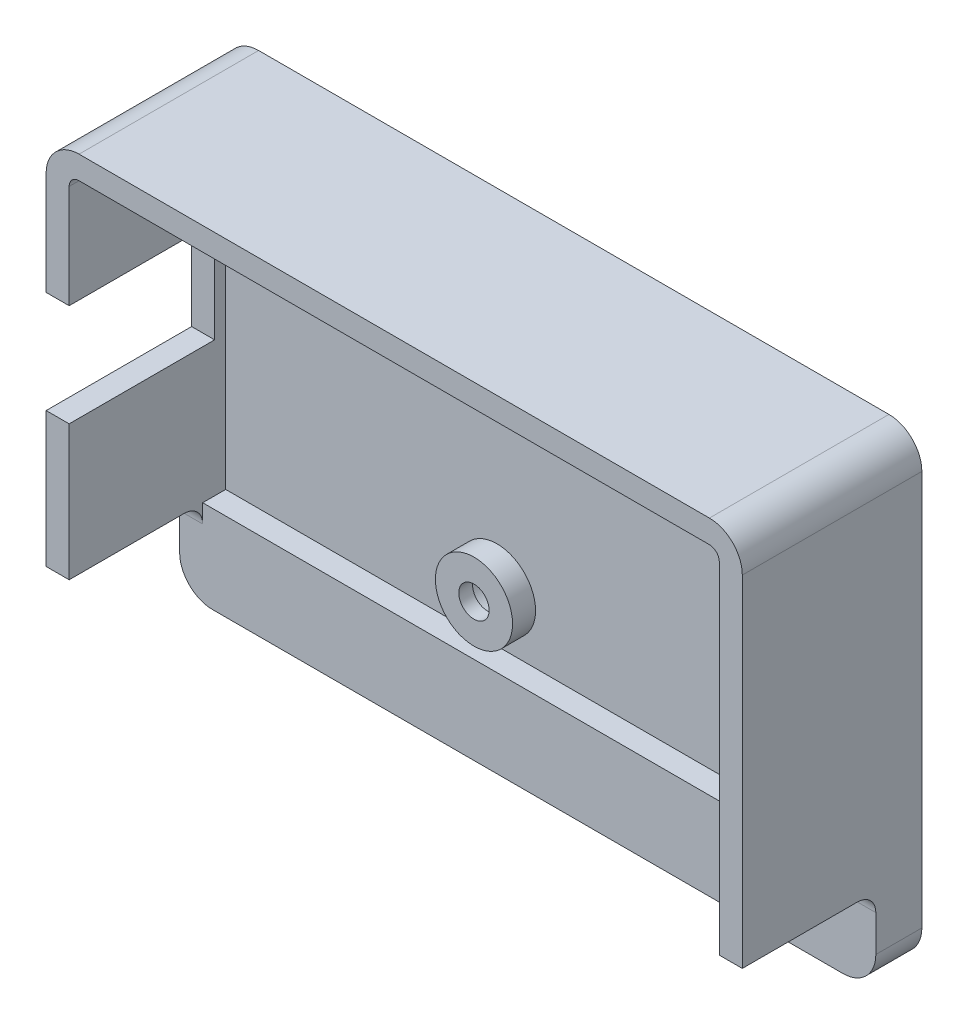
SolidWorks part; units mm, degrees
ref_plane "前视基准面" through (0, 0, 0) normal (0, 0, 1) x (1, 0, 0)
ref_plane "上视基准面" through (0, 0, 0) normal (0, 1, 0) x (1, 0, 0)
ref_plane "右视基准面" through (0, 0, 0) normal (1, 0, 0) x (0, 0, -1)
sketch "草图1" plane through (0, 0, 0) normal (0, 0, 1) x (1, 0, 0)
  line L0 (33.2419, -17.3338) -> (33.2419, -5.4548)
  line L4 (33.2419, -5.4548) -> (33.2419, 25.6013)
  line L5 (-36.2952, -18.4088) -> (32.1669, -18.4088)
  line L6 (-36.2952, 26.6762) -> (32.1669, 26.6762)
  line L7 (-37.3701, -17.3338) -> (-37.3701, 25.6013)
  line L8 (-37.3701, -11.3206) -> (33.2419, -11.3943)
  line L2616 (29.2206, 25.1602) -> (28.7969, 25.1936)
  line L2617 (28.7969, 25.1936) -> (28.3732, 25.1602)
  line L2618 (28.3732, 25.1602) -> (27.96, 25.061)
  line L2619 (27.96, 25.061) -> (27.5673, 24.8984)
  line L2620 (27.5673, 24.8984) -> (27.2049, 24.6763)
  line L2621 (27.2049, 24.6763) -> (26.8818, 24.4003)
  line L2622 (26.8818, 24.4003) -> (26.6058, 24.0772)
  line L2623 (26.6058, 24.0772) -> (26.3837, 23.7148)
  line L2624 (26.3837, 23.7148) -> (26.2211, 23.3222)
  line L2625 (26.2211, 23.3222) -> (26.1219, 22.9089)
  line L2626 (26.1219, 22.9089) -> (26.0885, 22.4852)
  line L2627 (26.0885, 22.4852) -> (26.1219, 22.0616)
  line L2628 (26.1219, 22.0616) -> (26.2211, 21.6483)
  line L2629 (26.2211, 21.6483) -> (26.3837, 21.2557)
  line L2630 (26.3837, 21.2557) -> (26.6058, 20.8933)
  line L2631 (26.6058, 20.8933) -> (26.8818, 20.5701)
  line L2632 (26.8818, 20.5701) -> (27.2049, 20.2941)
  line L2633 (27.2049, 20.2941) -> (27.5673, 20.0721)
  line L2634 (27.5673, 20.0721) -> (27.96, 19.9094)
  line L2635 (27.96, 19.9094) -> (28.3732, 19.8102)
  line L2636 (28.3732, 19.8102) -> (28.7969, 19.7769)
  line L2637 (28.7969, 19.7769) -> (29.2206, 19.8102)
  line L2638 (29.2206, 19.8102) -> (29.6338, 19.9094)
  line L2639 (29.6338, 19.9094) -> (30.0264, 20.0721)
  line L2640 (30.0264, 20.0721) -> (30.3888, 20.2941)
  line L2641 (30.3888, 20.2941) -> (30.712, 20.5701)
  line L2642 (30.712, 20.5701) -> (30.988, 20.8933)
  line L2643 (30.988, 20.8933) -> (31.21, 21.2557)
  line L2644 (31.21, 21.2557) -> (31.3727, 21.6483)
  line L2645 (31.3727, 21.6483) -> (31.4719, 22.0616)
  line L2646 (31.4719, 22.0616) -> (31.5052, 22.4852)
  line L2647 (31.5052, 22.4852) -> (31.4719, 22.9089)
  line L2648 (31.4719, 22.9089) -> (31.3727, 23.3222)
  line L2649 (31.3727, 23.3222) -> (31.21, 23.7148)
  line L2650 (31.21, 23.7148) -> (30.988, 24.0772)
  line L2651 (30.988, 24.0772) -> (30.712, 24.4003)
  line L2652 (30.712, 24.4003) -> (30.3888, 24.6763)
  line L2653 (30.3888, 24.6763) -> (30.0264, 24.8984)
  line L2654 (30.0264, 24.8984) -> (29.6338, 25.061)
  line L2655 (29.6338, 25.061) -> (29.2206, 25.1602)
  line L2808 (-6.6331, -8.3493) -> (-6.3142, -8.1539)
  line L2809 (-6.3142, -8.1539) -> (-5.991, -7.8779)
  line L2810 (-5.991, -7.8779) -> (-5.715, -7.5547)
  line L2811 (-5.715, -7.5547) -> (-5.493, -7.1923)
  line L2812 (-5.493, -7.1923) -> (-5.3303, -6.7997)
  line L2813 (-5.3303, -6.7997) -> (-5.2311, -6.3864)
  line L2814 (-5.2311, -6.3864) -> (-5.1978, -5.9628)
  line L2815 (-5.1978, -5.9628) -> (-5.2311, -5.5391)
  line L2816 (-5.2311, -5.5391) -> (-5.3303, -5.1258)
  line L2817 (-5.3303, -5.1258) -> (-5.493, -4.7332)
  line L2818 (-5.493, -4.7332) -> (-5.715, -4.3708)
  line L2819 (-5.715, -4.3708) -> (-5.991, -4.0477)
  line L2820 (-5.991, -4.0477) -> (-6.3142, -3.7717)
  line L2821 (-6.3142, -3.7717) -> (-6.6766, -3.5496)
  line L2822 (-6.6766, -3.5496) -> (-7.0692, -3.387)
  line L2823 (-7.0692, -3.387) -> (-7.4824, -3.2878)
  line L2824 (-7.4824, -3.2878) -> (-7.9061, -3.2544)
  line L2825 (-7.9061, -3.2544) -> (-8.3298, -3.2878)
  line L2826 (-8.3298, -3.2878) -> (-8.743, -3.387)
  line L2827 (-8.743, -3.387) -> (-9.1357, -3.5496)
  line L2828 (-9.1357, -3.5496) -> (-9.4981, -3.7717)
  line L2829 (-9.4981, -3.7717) -> (-9.8212, -4.0477)
  line L2830 (-9.8212, -4.0477) -> (-10.0972, -4.3708)
  line L2831 (-10.0972, -4.3708) -> (-10.3193, -4.7332)
  line L2832 (-10.3193, -4.7332) -> (-10.4819, -5.1258)
  line L2833 (-10.4819, -5.1258) -> (-10.5811, -5.5391)
  line L2834 (-10.5811, -5.5391) -> (-10.6145, -5.9628)
  line L2835 (-10.6145, -5.9628) -> (-10.5811, -6.3864)
  line L2836 (-10.5811, -6.3864) -> (-10.4819, -6.7997)
  line L2837 (-10.4819, -6.7997) -> (-10.3193, -7.1923)
  line L2838 (-10.3193, -7.1923) -> (-10.0972, -7.5547)
  line L2839 (-10.0972, -7.5547) -> (-9.8212, -7.8779)
  line L2840 (-9.8212, -7.8779) -> (-9.4981, -8.1539)
  line L2841 (-9.4981, -8.1539) -> (-9.1792, -8.3493)
  line L3455 (29.2206, 25.1602) -> (28.7969, 25.1936)
  line L3456 (28.7969, 25.1936) -> (28.3732, 25.1602)
  line L3457 (28.3732, 25.1602) -> (27.96, 25.061)
  line L3458 (27.96, 25.061) -> (27.5673, 24.8984)
  line L3459 (27.5673, 24.8984) -> (27.2049, 24.6763)
  line L3460 (27.2049, 24.6763) -> (26.8818, 24.4003)
  line L3461 (26.8818, 24.4003) -> (26.6058, 24.0772)
  line L3462 (26.6058, 24.0772) -> (26.3837, 23.7148)
  line L3463 (26.3837, 23.7148) -> (26.2211, 23.3222)
  line L3464 (26.2211, 23.3222) -> (26.1219, 22.9089)
  line L3465 (26.1219, 22.9089) -> (26.0885, 22.4852)
  line L3466 (26.0885, 22.4852) -> (26.1219, 22.0616)
  line L3467 (26.1219, 22.0616) -> (26.2211, 21.6483)
  line L3468 (26.2211, 21.6483) -> (26.3837, 21.2557)
  line L3469 (26.3837, 21.2557) -> (26.6058, 20.8933)
  line L3470 (26.6058, 20.8933) -> (26.8818, 20.5701)
  line L3471 (26.8818, 20.5701) -> (27.2049, 20.2941)
  line L3472 (27.2049, 20.2941) -> (27.5673, 20.0721)
  line L3473 (27.5673, 20.0721) -> (27.96, 19.9094)
  line L3474 (27.96, 19.9094) -> (28.3732, 19.8102)
  line L3475 (28.3732, 19.8102) -> (28.7969, 19.7769)
  line L3476 (28.7969, 19.7769) -> (29.2206, 19.8102)
  line L3477 (29.2206, 19.8102) -> (29.6338, 19.9094)
  line L3478 (29.6338, 19.9094) -> (30.0264, 20.0721)
  line L3479 (30.0264, 20.0721) -> (30.3888, 20.2941)
  line L3480 (30.3888, 20.2941) -> (30.712, 20.5701)
  line L3481 (30.712, 20.5701) -> (30.988, 20.8933)
  line L3482 (30.988, 20.8933) -> (31.21, 21.2557)
  line L3483 (31.21, 21.2557) -> (31.3727, 21.6483)
  line L3484 (31.3727, 21.6483) -> (31.4719, 22.0616)
  line L3485 (31.4719, 22.0616) -> (31.5052, 22.4852)
  line L3486 (31.5052, 22.4852) -> (31.4719, 22.9089)
  line L3487 (31.4719, 22.9089) -> (31.3727, 23.3222)
  line L3488 (31.3727, 23.3222) -> (31.21, 23.7148)
  line L3489 (31.21, 23.7148) -> (30.988, 24.0772)
  line L3490 (30.988, 24.0772) -> (30.712, 24.4003)
  line L3491 (30.712, 24.4003) -> (30.3888, 24.6763)
  line L3492 (30.3888, 24.6763) -> (30.0264, 24.8984)
  line L3493 (30.0264, 24.8984) -> (29.6338, 25.061)
  line L3494 (29.6338, 25.061) -> (29.2206, 25.1602)
  line L4236 (-7.4824, -3.2878) -> (-7.9061, -3.2544)
  line L4237 (-7.9061, -3.2544) -> (-8.3298, -3.2878)
  line L4238 (-8.3298, -3.2878) -> (-8.743, -3.387)
  line L4239 (-8.743, -3.387) -> (-9.1357, -3.5496)
  line L4240 (-9.1357, -3.5496) -> (-9.4981, -3.7717)
  line L4241 (-9.4981, -3.7717) -> (-9.8212, -4.0477)
  line L4242 (-9.8212, -4.0477) -> (-10.0972, -4.3708)
  line L4243 (-10.0972, -4.3708) -> (-10.3193, -4.7332)
  line L4244 (-10.3193, -4.7332) -> (-10.4819, -5.1258)
  line L4245 (-10.4819, -5.1258) -> (-10.5811, -5.5391)
  line L4246 (-10.5811, -5.5391) -> (-10.6145, -5.9628)
  line L4247 (-10.6145, -5.9628) -> (-10.5811, -6.3864)
  line L4248 (-10.5811, -6.3864) -> (-10.4819, -6.7997)
  line L4249 (-10.4819, -6.7997) -> (-10.3193, -7.1923)
  line L4250 (-10.3193, -7.1923) -> (-10.0972, -7.5547)
  line L4251 (-10.0972, -7.5547) -> (-9.8212, -7.8779)
  line L4252 (-9.8212, -7.8779) -> (-9.4981, -8.1539)
  line L4253 (-9.4981, -8.1539) -> (-9.1357, -8.3759)
  line L4254 (-9.1357, -8.3759) -> (-8.743, -8.5386)
  line L4255 (-8.743, -8.5386) -> (-8.3298, -8.6378)
  line L4256 (-8.3298, -8.6378) -> (-7.9061, -8.6711)
  line L4257 (-7.9061, -8.6711) -> (-7.4824, -8.6378)
  line L4258 (-7.4824, -8.6378) -> (-7.0692, -8.5386)
  line L4259 (-7.0692, -8.5386) -> (-6.6766, -8.3759)
  line L4260 (-6.6766, -8.3759) -> (-6.3142, -8.1539)
  line L4261 (-6.3142, -8.1539) -> (-5.991, -7.8779)
  line L4262 (-5.991, -7.8779) -> (-5.715, -7.5547)
  line L4263 (-5.715, -7.5547) -> (-5.493, -7.1923)
  line L4264 (-5.493, -7.1923) -> (-5.3303, -6.7997)
  line L4265 (-5.3303, -6.7997) -> (-5.2311, -6.3864)
  line L4266 (-5.2311, -6.3864) -> (-5.1978, -5.9628)
  line L4267 (-5.1978, -5.9628) -> (-5.2311, -5.5391)
  line L4268 (-5.2311, -5.5391) -> (-5.3303, -5.1258)
  line L4269 (-5.3303, -5.1258) -> (-5.493, -4.7332)
  line L4270 (-5.493, -4.7332) -> (-5.715, -4.3708)
  line L4271 (-5.715, -4.3708) -> (-5.991, -4.0477)
  line L4272 (-5.991, -4.0477) -> (-6.3142, -3.7717)
  line L4273 (-6.3142, -3.7717) -> (-6.6766, -3.5496)
  line L4274 (-6.6766, -3.5496) -> (-7.0692, -3.387)
  line L4275 (-7.0692, -3.387) -> (-7.4824, -3.2878)
  line L6751 (-40.2351, 12.9602) -> (-37.3701, 12.9602)
  line L6763 (-40.2351, 4.0702) -> (-37.3701, 4.1337)
  line L6764 (-40.2351, 4.0702) -> (-40.2351, 12.9602)
  circle A1 centre (33.2419, -5.4548) radius 0.04
  circle A3 centre (33.2419, -5.4548) radius 0.04
  circle A7 centre (33.2419, -5.4548) radius 0.04
  circle A8 centre (33.2419, -5.4548) radius 0.04
  arc A1492 (32.1669, -18.4088) -> (33.2419, -17.3338) centre (32.1669, -17.3338) ccw
  arc A1495 (33.2419, 25.6013) -> (32.1669, 26.6762) centre (32.1669, 25.6013) ccw
  arc A1498 (-36.2952, 26.6762) -> (-37.3701, 25.6013) centre (-36.2952, 25.6013) ccw
  arc A1501 (-37.3701, -17.3338) -> (-36.2952, -18.4088) centre (-36.2952, -17.3338) ccw
  circle A1904 centre (28.7969, 22.4852) radius 1.25
  circle A1905 centre (28.7969, 22.4852) radius 1.3008
  circle A1906 centre (28.7969, 22.4852) radius 1.25
  circle A1907 centre (28.7969, 22.4852) radius 1.25
  circle A1908 centre (28.7969, 22.4852) radius 1.3008
  circle A1909 centre (28.7969, 22.4852) radius 0.8
  circle A1910 centre (-7.9061, -5.9628) radius 1.25
  circle A1911 centre (-7.9061, -5.9628) radius 1.3008
  circle A1912 centre (-7.9061, -5.9628) radius 1.25
  circle A1913 centre (-7.9061, -5.9628) radius 1.25
  circle A1914 centre (-7.9061, -5.9628) radius 1.3008
  circle A1915 centre (-7.9061, -5.9628) radius 0.8
  circle A2317 centre (32.4709, 10.6882) radius 0.0635
  circle A2321 centre (32.4709, 10.6882) radius 0.0635
  circle A3495 centre (-40.2351, 12.9602) radius 0.0381
  circle A3503 centre (-37.3701, 4.1337) radius 0.0381
  circle A3517 centre (-37.3701, 4.1337) radius 0.0381
  circle A3521 centre (-40.2351, 4.0702) radius 0.0381
  circle A3522 centre (-37.3701, 4.1337) radius 0.0381
  circle A3523 centre (-40.2351, 4.0702) radius 0.0381
  circle A3524 centre (-40.2351, 12.9602) radius 0.0381
  circle A3525 centre (-36.7351, 11.6902) radius 0.0381
  circle A3529 centre (-36.7351, 5.3402) radius 0.0381
  dimension "D1" = 70.612
  dimension "D2" = 45.085
sketch "草图4" plane through (0, 0, 0) normal (0, 0, 1) x (1, 0, 0)
  line L1 (32.1649, -18.4088) -> (-36.2951, -18.4088)
  line L2 (33.2399, -17.3338) -> (33.2399, 25.6062)
  line L3 (32.1649, 26.6812) -> (-36.2951, 26.6812)
  line L4 (-37.3701, -17.3338) -> (-37.3701, 25.6062)
  line L5 (33.2399, -18.4088) -> (-37.3701, 26.6812) construction
  line L6 (33.2399, 26.6812) -> (-37.3701, -18.4088) construction
  arc A0 (32.1649, -18.4088) -> (33.2399, -17.3338) centre (32.1649, -17.3338) ccw
  arc A1 (-36.2951, -18.4088) -> (-37.3701, -17.3338) centre (-36.2951, -17.3338) cw
  arc A2 (-37.3701, 25.6062) -> (-36.2951, 26.6812) centre (-36.2951, 25.6062) cw
  arc A3 (33.2399, 25.6062) -> (32.1649, 26.6812) centre (32.1649, 25.6062) ccw
  point P0 (-2.0651, 4.1362)
  dimension "D3" = 1.075
  dimension "D1" = 70.61
  dimension "D2" = 45.09
extrude "凸台-拉伸1" add sketch "草图4" along normal blind 17
shell "抽壳1" thickness 2.5 removed face at (-2.0651, 4.1362, 17) outward yes
sketch "草图5" plane through (0, 0, 0) normal (0, 0, 1) x (1, 0, 0)
  line L0 (-36.2952, 26.6762) -> (32.1669, 26.6762) construction
  circle A0 centre (28.7969, 22.4852) radius 4.191
  circle A1 centre (-7.9061, -5.9628) radius 4.191
extrude "凸台-拉伸2" add sketch "草图5" along normal blind 2.5
sketch "草图6" plane through (0, 0, 0) normal (0, 0, 1) x (1, 0, 0)
  circle A0 centre (-7.9061, -5.9628) radius 2.7083
  circle A1 centre (28.7969, 22.4852) radius 2.7083
extrude "切除-拉伸1" cut sketch "草图6" against normal up to next and the other way blind 1
sketch "草图7" plane through (0, 0, 0) normal (0, 0, 1) x (1, 0, 0)
  circle A0 centre (-7.9061, -5.9628) radius 1.65
  circle A1 centre (28.7969, 22.4852) radius 1.65
extrude "切除-拉伸2" cut sketch "草图7" against normal through all both and the other way through all
sketch "草图8" plane through (-39.8701, 0, 0) normal (-1, 0, 0) x (0, 0, 1)
  line L1 (1.2, 3.2764) -> (1.2, 14.3847)
  line L2 (-2.5, 25.6062) -> (-2.5, -17.3338) construction
  line L3 (1.2, 3.2764) -> (17, 3.2764)
  line L4 (17, 25.6062) -> (17, -17.3338) construction
  line L5 (17, 3.2764) -> (17, 14.3847)
  line L6 (17, 14.3847) -> (1.2, 14.3847)
  dimension "D1" = 3.7
extrude "切除-拉伸3" cut sketch "草图8" against normal blind 3
sketch "草图9" plane through (0, 0, 0) normal (0, 0, 1) x (1, 0, 0)
  line L0 (35.7399, -11.3943) -> (-39.8701, -11.3943)
  line L1 (-39.8701, 3.2764) -> (-39.8701, -17.3338) construction
  line L2 (-39.8701, -11.3943) -> (-39.8701, -20.9088)
  line L3 (35.7399, -11.3943) -> (35.7399, -20.9088)
  line L4 (35.7399, -17.3338) -> (35.7399, 25.6062) construction
  line L5 (-39.8701, -20.9088) -> (35.7399, -20.9088)
extrude "切除-拉伸4" cut sketch "草图9" along normal up to next
sketch "草图10" plane through (0, 0, 0) normal (0, 0, 1) x (1, 0, 0)
  line L0 (-39.8701, -11.3943) -> (35.7399, -11.3943)
  line L1 (35.7399, -11.3943) -> (35.7399, -17.3338)
  line L2 (-39.8701, -11.3943) -> (-39.8701, -17.3338)
  line L3 (-36.2951, -20.9088) -> (32.1649, -20.9088)
  arc A0 (32.1649, -20.9088) -> (35.7399, -17.3338) centre (32.1649, -17.3338) ccw
  arc A1 (-36.2951, -20.9088) -> (-39.8701, -17.3338) centre (-36.2951, -17.3338) cw
extrude "凸台-拉伸3" add sketch "草图10" along normal blind 2.5
fillet "圆角1" radius 2 2 edges at (34.4899, -11.3943, 2.5) (-38.6201, -11.3943, 2.5)
